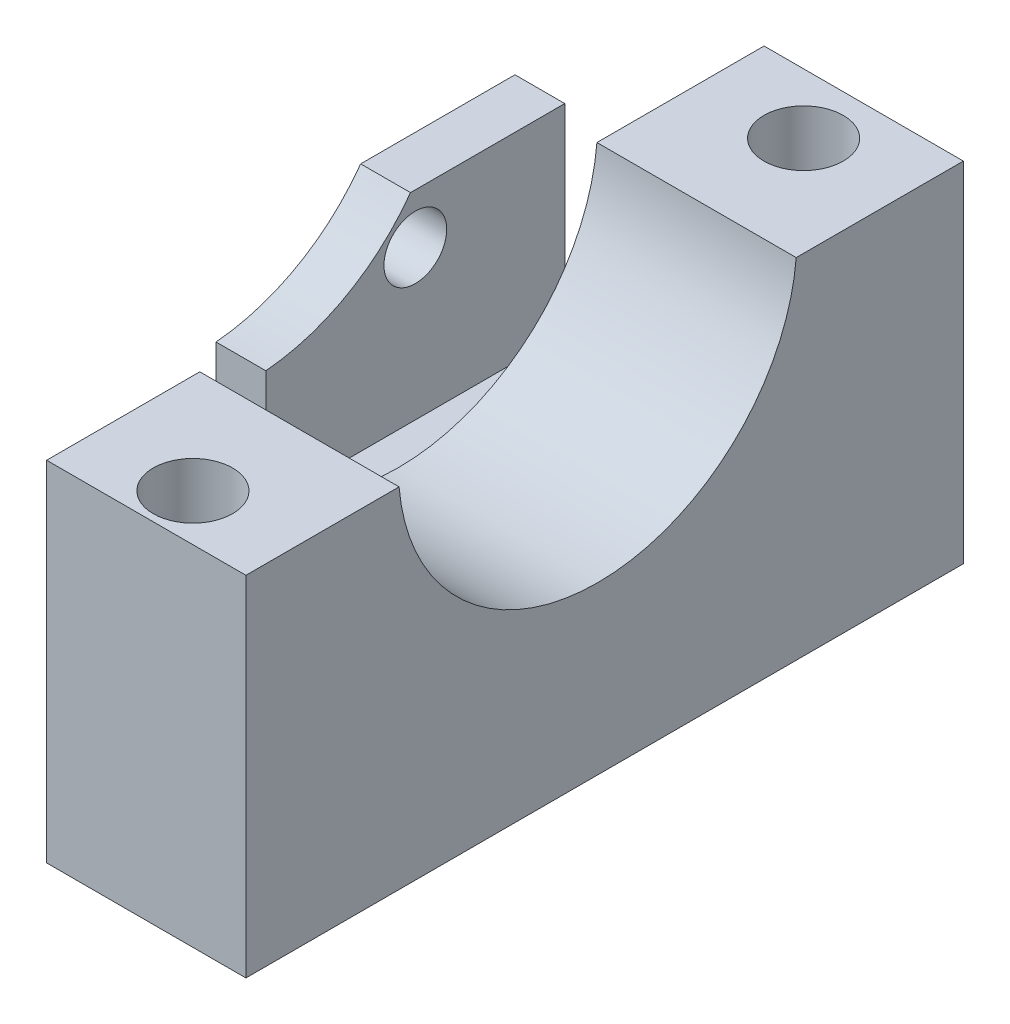
SolidWorks part; units mm, degrees
material "ABS"
ref_plane "Front Plane" through (0, 0, 0) normal (0, 0, 1) x (1, 0, 0)
ref_plane "Top Plane" through (0, 0, 0) normal (0, 1, 0) x (1, 0, 0)
ref_plane "Right Plane" through (0, 0, 0) normal (1, 0, 0) x (0, 0, -1)
sketch "Sketch1" plane through (0, 0, 0) normal (0, 1, 0) x (1, 0, 0)
  line L0 (-3.175, 9.525) -> (-3.175, -9.525)
  line L1 (-6.35, -9.525) -> (6.35, -9.525)
  line L2 (-6.35, -9.525) -> (-6.35, 9.525)
  line L3 (-6.35, 9.525) -> (6.35, 9.525)
  line L4 (6.35, -9.525) -> (6.35, 9.525)
  line L5 (-6.35, -9.525) -> (6.35, 9.525) construction
  line L6 (-6.35, 9.525) -> (6.35, -9.525) construction
  point P0 (0, 0)
  dimension "D1" = 12.7
  dimension "D2" = 3.175
  dimension "D3" = 19.05
extrude "Boss-Extrude1" add sketch "Sketch1" along normal blind 3.175 contours L1 L4 L3 L0 | L3 L2 L1 L0 region at (1.5875, 0, 0) region at (-4.7625, 0, 0)
extrude "Boss-Extrude2" add sketch "Sketch1<3>" along normal blind 12.7 from surface contours L3 L2 L1 L0 region at (-4.7625, 0, 0) starting at face at (0, 3.175, 0)
sketch "Sketch1<3>" plane through (0, 0, 0) normal (0, 1, 0) x (1, 0, 0) same geometry as "Sketch1"
sketch "Sketch2" plane through (-3.175, 0, 0) normal (1, 0, 0) x (0, 0, -1)
  line L0 (0, 15.875) -> (0, 12.7) construction
  line L1 (-9.525, 15.875) -> (9.525, 15.875) construction
  circle A0 centre (0, 12.7) radius 2
  point P6 (0, 11.012)
  dimension "D1" = 4
  dimension "D2" = 3.175
extrude "Cut-Extrude1" cut sketch "Sketch2" against normal through all
sketch "Sketch4" plane through (0, 0, 0) normal (0, -1, 0) x (1, 0, 0)
  line L0 (12.7, -12.7) -> (12.7, 33.02) construction
  line L1 (6.35, -12.7) -> (19.05, -12.7)
  line L2 (6.35, -12.7) -> (6.35, 33.02)
  line L3 (6.35, 33.02) -> (19.05, 33.02)
  line L4 (19.05, -12.7) -> (19.05, 33.02)
  line L5 (-3.175, -9.525) -> (6.35, -9.525) construction
  line L6 (6.35, 9.525) -> (6.35, -9.525) construction
  circle A0 centre (12.7, -6.0678) radius 1.9844 construction
  circle A1 centre (12.7, 25.6115) radius 1.9844 construction
  point P11 (6.35, -9.525)
  point P13 (13.0486, -5.6957)
  point P14 (6.4164, -12.3279)
  dimension "D2" = 3.9688
  dimension "D1" = 45.72
  dimension "D3" = 3.175
  dimension "D4" = 12.7
extrude "Boss-Extrude3" add sketch "Sketch4" against normal blind 22.225
sketch "Sketch3" plane through (-6.35, 0, 0) normal (-1, 0, 0) x (0, 0, 1)
  line L0 (0, 12.7) -> (10.6066, 23.3066) construction
  line L1 (0, 12.7) -> (9.525, 12.7) construction
  line L2 (9.525, 15.875) -> (9.525, 0) construction
  circle A0 centre (0, 12.7) radius 10 construction
  circle A1 centre (10.6066, 23.3066) radius 5 construction
  circle A2 centre (10.6066, 23.3066) radius 12.5 construction
  circle A3 centre (10.6066, 23.3066) radius 12.7
  dimension "D1" = 10
  dimension "D2" = 20
  dimension "D4" = 25
  dimension "D5" = 25.4
  dimension "D3" = 45
extrude "Cut-Extrude2" cut sketch "Sketch3" against normal through all
hole_wizard "#8 (0.199) Diameter Hole1" positions "Sketch5" profile "Sketch6" hole size "#8" standard "ANSI Inch"
sketch "Sketch5" plane through (0, 22.225, 0) normal (0, 1, 0) x (1, 0, 0)
  point P0 (12.7, 8.8685)
  point P2 (12.7, -30.0473)
sketch "Sketch6" plane through (12.7, 22.225, -8.8685) normal (1, 0, 0) x (0, 0, 1)
  line L0 (0, 0) -> (0, 62.9866)
  line L1 (0, 62.9866) -> (2.5273, 61.468)
  line L2 (2.5273, 61.468) -> (2.5273, 0)
  line L5 (2.5273, 0) -> (0, 0)
  line L10 (0, 62.9866) -> (-2.5273, 61.468) construction
  line L11 (0, -6.35) -> (0, 107.95) construction
  dimension "Hole Dia." = 5.0546
  dimension "Hole Depth" = 61.468
  dimension "Drill Angle" = 118
